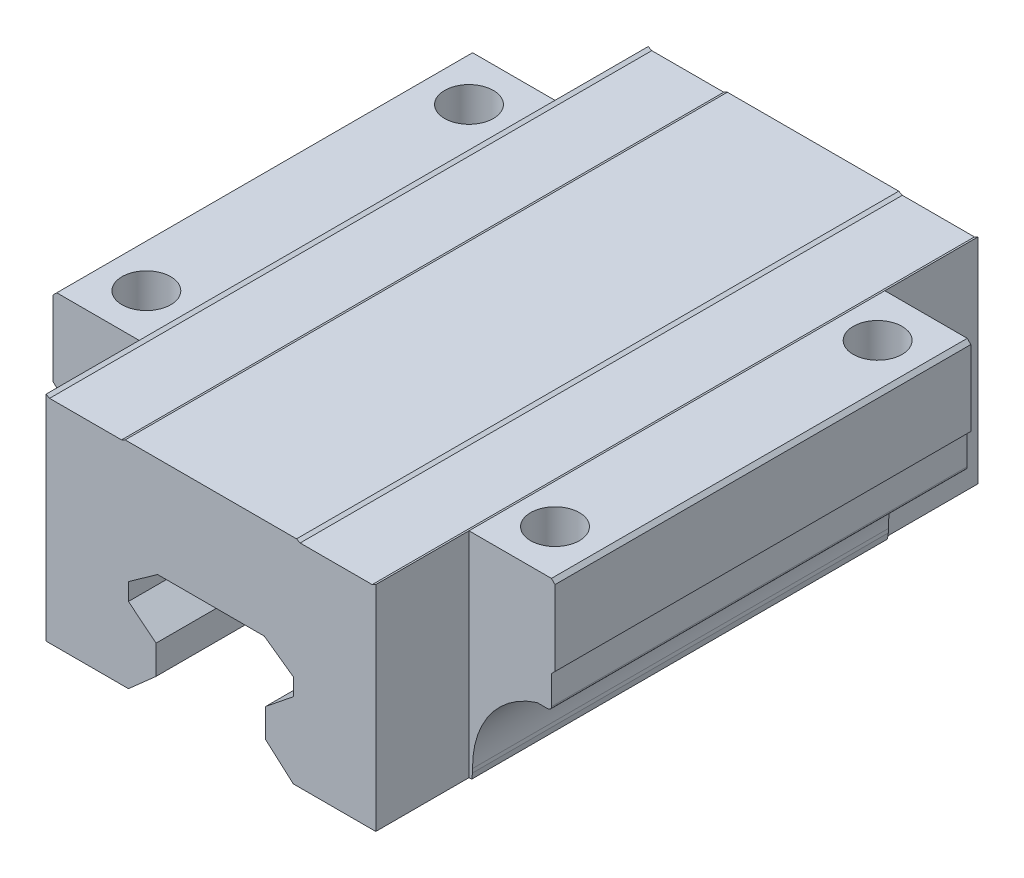
SolidWorks part; units mm, degrees
note: The reader was unsure of these and kept them because the rebuilt part matched: shared geometry of "草图1<5>".
ref_plane "前视基准面" through (0, 0, 0) normal (0, 0, 1) x (1, 0, 0)
ref_plane "上视基准面" through (0, 0, 0) normal (0, 1, 0) x (1, 0, 0)
ref_plane "右视基准面" through (0, 0, 0) normal (1, 0, 0) x (0, 0, -1)
sketch "草图1" plane through (0, 0, 0) normal (0, 0, 1) x (1, 0, 0)
  line L0 (-87.1056, 0) -> (87.1056, 0) construction
  line L1 (0, 87.1056) -> (0, -87.1056) construction
  line L3 (-7.6477, 9.1456) -> (-7.6477, 13.1661)
  line L4 (-11.5012, 16.2697) -> (-11.5012, 18.6697)
  line L5 (-11.5001, 5.735) -> (-7.6477, 9.1456)
  line L6 (-7.4353, 21.5617) -> (7.4384, 21.5595)
  line L7 (-11.5012, 16.2697) -> (-7.6477, 13.1661)
  line L8 (-7.4353, 21.5617) -> (-11.5012, 18.6697)
  line L9 (-32.5, 19.5606) -> (-34, 19.5606)
  line L10 (-34.5, 20.0606) -> (-34.5, 24.0606)
  line L11 (-34.5, 24.0606) -> (-35, 24.5606)
  line L12 (-35, 24.5606) -> (-35, 35.0606)
  line L13 (-35, 35.0606) -> (-34.5, 35.5606)
  line L14 (-34.5, 35.5606) -> (-23, 35.5606)
  line L15 (-23, 35.5606) -> (-22.5, 35.3106)
  line L16 (-22.5, 35.3106) -> (-12.4586, 35.3106)
  line L17 (-12.4586, 35.3106) -> (-11.9586, 35.5606)
  line L18 (-11.9586, 35.5606) -> (11.9471, 35.5606)
  line L19 (11.9471, 35.5606) -> (12.4471, 35.3106)
  line L20 (12.4471, 35.3106) -> (22.5, 35.3106)
  line L21 (22.5, 35.3106) -> (23, 35.5606)
  line L22 (23, 35.5606) -> (34.5, 35.5606)
  line L23 (34.5, 35.5606) -> (35, 35.0606)
  line L24 (35, 35.0606) -> (35, 24.5606)
  line L25 (35, 24.5606) -> (34.5, 24.0606)
  line L26 (34.5, 24.0606) -> (34.5, 20.0606)
  line L27 (34, 19.5606) -> (32.5, 19.5606)
  line L28 (23.5, 7.0917) -> (23.5, 6.5604)
  line L29 (23.5, 6.5604) -> (23.3678, 5.7348)
  line L30 (23.3678, 5.7348) -> (11.5001, 5.735)
  line L31 (11.5001, 5.735) -> (11.5, 0.0606)
  line L32 (11.5, 0.0606) -> (11, -0.4394)
  line L33 (11, -0.4394) -> (2.0008, -0.4394)
  line L34 (2.0008, -0.4394) -> (1.65, 0)
  line L35 (1.65, 0) -> (-1.65, 0)
  line L36 (-1.65, 0) -> (-2.0008, -0.4394)
  line L37 (-2.0008, -0.4394) -> (-11, -0.4394)
  line L38 (-11, -0.4394) -> (-11.5, 0.0606)
  line L39 (-11.5, 0.0606) -> (-11.5001, 5.735)
  line L40 (-11.5001, 5.735) -> (-23.3679, 5.7347)
  line L41 (-23.3679, 5.7347) -> (-23.5, 6.5604)
  line L42 (-23.5, 6.5604) -> (-23.5, 7.0917)
  line L44 (7.6477, 9.1456) -> (7.6477, 13.1661)
  line L45 (11.5012, 16.2697) -> (11.5012, 18.6697)
  line L46 (11.5001, 5.735) -> (7.6477, 9.1456)
  line L47 (11.5012, 16.2697) -> (7.6477, 13.1661)
  line L48 (7.4384, 21.5595) -> (11.5012, 18.6697)
  line L49 (23, 35.5606) -> (22.9996, 5.7348)
  line L50 (-23, 35.5606) -> (-22.9996, 5.7347)
  arc A0 (-34.5, 20.0606) -> (-34, 19.5606) centre (-34, 20.0606) ccw
  arc A1 (34, 19.5606) -> (34.5, 20.0606) centre (34, 20.0606) ccw
  arc A2 (32.5, 19.5606) -> (23.5, 7.0917) centre (36.3558, 7.2949) ccw
  arc A3 (-23.5, 7.0917) -> (-32.5, 19.5606) centre (-36.3558, 7.2949) ccw
extrude "凸台-拉伸1" add sketch "草图1" along normal mid plane 84 contours L15 L50 L40 L5 L3 L7 L4 L8 L6 L48 L45 L47 L44 L46 L30 L49 L21 L20 L19 L18 L17 L16
extrude "凸台-拉伸2" add sketch "草图1<5>" along normal mid plane 58 separate body contours A2 L27 A1 L26 L25 L24 L23 L22 L49 L30 L29 L28 | A3 L42 L41 L40 L50 L14 L13 L12 L11 L10 A0 L9
sketch "草图1<5>" plane through (0, 0, 0) normal (0, 0, 1) x (1, 0, 0) same geometry as "草图1"
hole_wizard "M8 螺纹孔1" positions "草图3" profile "草图2" tap size "M8" standard "GB"
sketch "草图3" plane through (-5.7295, 35.5606, -2.5337) normal (0, 1, 0) x (-1, 0, 0)
  line L0 (16.7705, 2.5337) -> (-28.2295, 2.5337) construction
  line L1 (16.7705, 44.5337) -> (16.7705, -39.4663) construction
  line L2 (-28.2295, 44.5337) -> (-28.2295, -39.4663) construction
  line L4 (-5.7295, 2.5337) -> (-5.7295, -41.7061) construction
  point P0 (22.7705, 25.0337)
  point P1 (22.7705, -19.9663)
  point P3 (-34.2295, -19.9663)
  point P5 (-34.2295, 25.0337)
  dimension "D1" = 45
  dimension "D2" = 57
sketch "草图2" plane through (-28.5, 35.5606, 22.5) normal (1, 0, 0) x (0, 0, 1)
  line L0 (0, 0) -> (0, 21.7929)
  line L1 (0, 21.7929) -> (3.4, 19.75)
  line L2 (3.4, 19.75) -> (3.4, 0)
  line L5 (3.4, 0) -> (0, 0)
  line L10 (0, 21.7929) -> (-3.4, 19.75) construction
  line L11 (0, -6.35) -> (0, 107.95) construction
  dimension "螺纹孔钻头直径" = 6.8
  dimension "螺纹孔钻头深度" = 19.75
  dimension "导头角度" = 118
cosmetic thread "孔螺蚊线1" parameters "D1"=16, "D2"=8
cosmetic thread "孔螺蚊线2" parameters "D1"=16, "D2"=8
cosmetic thread "孔螺蚊线3" parameters "D1"=16, "D2"=8
cosmetic thread "孔螺蚊线4" parameters "D1"=16, "D2"=8
